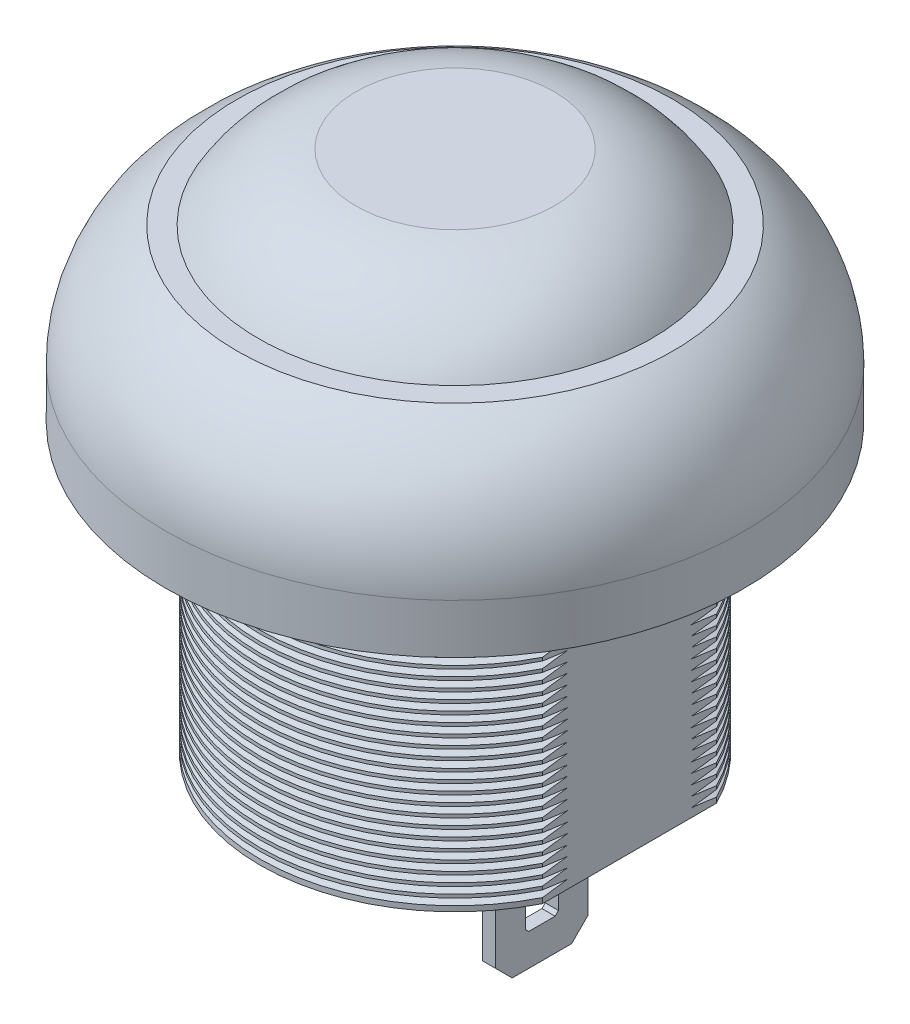
SolidWorks part; units mm, degrees
ref_plane "Front Plane" through (0, 0, 0) normal (0, 0, 1) x (1, 0, 0)
ref_plane "Top Plane" through (0, 0, 0) normal (0, 1, 0) x (1, 0, 0)
ref_plane "Right Plane" through (0, 0, 0) normal (1, 0, 0) x (0, 0, -1)
sketch "Sketch1" plane through (0, 0, 0) normal (0, 1, 0) x (1, 0, 0)
  circle A0 centre (0, 0) radius 8.75
  dimension "D1" = 17.5
extrude "Boss-Extrude1" add sketch "Sketch1" along normal blind 1.5
ref_plane "Plane1" through (0, 5.15, 0) normal (0, -1, 0) x (-1, 0, 0)
sketch "Sketch2" plane through (0, 5.15, 0) normal (0, -1, 0) x (-1, 0, 0)
  circle A0 centre (0, 0) radius 6.6
  dimension "D1" = 13.2
sketch "Sketch3" plane through (0, 0, 0) normal (0, 0, 1) x (1, 0, 0)
  line L0 (-6.6, 5.15) -> (6.6, 5.15) construction
  line L1 (-8.75, 1.5) -> (-8.75, 0) construction
  line L2 (-8.75, 0) -> (8.75, 0) construction
  line L3 (-8.75, 1.5) -> (0, 1.5)
  line L4 (8.75, 1.5) -> (-8.75, 1.5) construction
  line L5 (0, 1.5) -> (0, 5.15)
  line L6 (0, 5.15) -> (-6.6, 5.15)
  line L7 (0, 1.5) -> (0, 6.9701) construction
  arc A0 (-8.75, 1.5) -> (-6.6, 5.15) centre (-4.5767, 1.5) cw
revolve "Revolve1" add sketch "Sketch3" angle 360 about L7
ref_plane "Plane2" through (0, 7.15, 0) normal (0, 1, 0) x (1, 0, 0)
sketch "Sketch4" plane through (0, 7.15, 0) normal (0, 1, 0) x (1, 0, 0)
  circle A0 centre (0, 0) radius 3
  dimension "D1" = 6
sketch "Sketch5" plane through (0, 5.15, 0) normal (0, 1, 0) x (1, 0, 0)
  circle A0 centre (0, 0) radius 5.95
  dimension "D1" = 11.9
sketch "Sketch6" plane through (0, 0, 0) normal (0, 0, 1) x (1, 0, 0)
  line L0 (3, 7.15) -> (-3, 7.15) construction
  line L1 (5.95, 5.15) -> (-5.95, 5.15) construction
  line L2 (-3, 7.15) -> (0, 7.15)
  line L3 (0, 7.15) -> (0, 5.15)
  line L4 (0, 5.15) -> (-5.95, 5.15)
  line L5 (-5.95, 5.15) -> (-5.9731, 5.149)
  line L6 (0, 5.15) -> (0, 8.6522) construction
  arc A0 (-3, 7.15) -> (-5.95, 5.15) centre (-2.3574, 3.0265) ccw
  arc A1 (-6.6, 5.15) -> (-8.75, 1.5) centre (-4.5767, 1.5) ccw construction
revolve "Revolve2" add sketch "Sketch6" angle 360 about L6 region at (-2.5359, 6.0636, 0)
sketch "Sketch7" plane through (0, 0, 0) normal (0, -1, 0) x (1, 0, 0)
  circle A0 centre (0, 0) radius 6.61
  dimension "D1" = 13.22
extrude "Boss-Extrude2" add sketch "Sketch7" along normal blind 1.12
sketch "Sketch8" plane through (0, -1.12, 0) normal (0, -1, 0) x (1, 0, 0)
  circle A0 centre (0, 0) radius 5.9
  dimension "D1" = 11.8
extrude "Boss-Extrude3" add sketch "Sketch8" along normal blind 7.56
sketch "Sketch9" plane through (0, -8.68, 0) normal (0, -1, 0) x (1, 0, 0)
  circle A0 centre (0, 0) radius 4.34
  dimension "D1" = 8.68
extrude "Boss-Extrude4" add sketch "Sketch9" along normal blind 0.7
sketch "Sketch10" plane through (0, 0, 0) normal (0, 0, 1) x (1, 0, 0)
  line L0 (-4.34, -9.38) -> (4.34, -9.38) construction
  line L1 (-2.63, -9.38) -> (-2.23, -9.38)
  line L2 (-2.63, -9.38) -> (-2.63, -12.82)
  line L3 (-2.63, -12.82) -> (-2.23, -12.82)
  line L4 (-2.23, -9.38) -> (-2.23, -12.82)
  line L5 (-2.23, -9.38) -> (2.23, -9.38) construction
  line L6 (2.23, -9.38) -> (2.63, -9.38)
  line L7 (2.23, -9.38) -> (2.23, -12.82)
  line L8 (2.23, -12.82) -> (2.63, -12.82)
  line L9 (2.63, -9.38) -> (2.63, -12.82)
  line L10 (0, -9.38) -> (0, 0) construction
  dimension "D1" = 4.46
  dimension "D2" = 0.4
  dimension "D3" = 0.4
  dimension "D4" = 3.44
extrude "Boss-Extrude5" add sketch "Sketch10" along normal blind 1.4 and the other way blind 1.4
chamfer "Chamfer1" distance 0.5 distance2 0.5 4 edges at (-2.43, -12.82, -1.4) (-2.43, -12.82, 1.4) (2.43, -12.82, -1.4) (2.43, -12.82, 1.4)
sketch "Sketch11" plane through (2.63, 0, 0) normal (1, 0, 0) x (0, 0, -1)
  line L0 (0, -9.38) -> (0, -12.82) construction
  line L1 (1.4, -9.38) -> (-1.4, -9.38) construction
  line L2 (0.9, -12.82) -> (-0.9, -12.82) construction
  line L3 (0.5, -10.45) -> (0.4, -10.35)
  line L4 (-0.4, -11.85) -> (0.4, -11.85)
  line L5 (-0.5, -11.75) -> (-0.5, -10.45)
  line L6 (-0.4, -10.35) -> (0.4, -10.35)
  line L7 (0.5, -11.75) -> (0.5, -10.45)
  line L8 (-0.5, -11.85) -> (0.5, -10.35) construction
  line L9 (-0.5, -10.35) -> (0.5, -11.85) construction
  line L10 (-0.5, -10.45) -> (-0.4, -10.35)
  line L11 (-0.4, -11.85) -> (-0.5, -11.75)
  line L12 (0.4, -11.85) -> (0.5, -11.75)
  point P6 (0, -11.1)
  dimension "D1" = 1.5
  dimension "D2" = 1
extrude "Cut-Extrude1" cut sketch "Sketch11" against normal through all
sketch "Sketch12" plane through (0, -8.68, 0) normal (0, -1, 0) x (1, 0, 0)
  line L0 (5.28, 2.6328) -> (5.28, -2.6328)
  line L1 (-5.28, 2.6328) -> (-5.28, -2.6328)
  line L2 (-5.28, 0) -> (5.28, 0) construction
  arc A0 (5.28, -2.6328) -> (5.28, 2.6328) centre (0, 0) ccw
  circle A1 centre (0, 0) radius 5.9
  arc A2 (-5.28, 2.6328) -> (-5.28, -2.6328) centre (0, 0) ccw
  dimension "D2" = 10.56
  dimension "D1" = 0
extrude "Cut-Extrude2" cut sketch "Sketch12" against normal up to surface (7.56 mm away) up to face at (0, -1.12, -6.61)
sketch "Sketch13" plane through (0, -1.12, 0) normal (0, -1, 0) x (1, 0, 0)
  line L0 (-2.9803, 5.9) -> (2.9803, 5.9)
  arc A0 (5.28, 2.6328) -> (-5.28, 2.6328) centre (0, 0) ccw construction
  circle A1 centre (0, 0) radius 6.61
  arc A2 (2.9803, 5.9) -> (-2.9803, 5.9) centre (0, 0) ccw
  dimension "D1" = 0
extrude "Cut-Extrude3" cut sketch "Sketch13" against normal up to surface (1.12 mm away) up to face at (0, 0, 8.75)
sketch "Sketch14" plane through (0, 0, 0) normal (1, 0, 0) x (0, 0, -1)
  line L0 (-5.9, -1.12) -> (-5.6, -1.22)
  line L1 (-5.6, -1.22) -> (-5.9, -1.32)
  line L2 (-5.9, -1.12) -> (-5.9, -8.68) construction
  line L3 (-5.9, -1.32) -> (-5.9, -1.12)
  line L4 (-5.9, -1.22) -> (-5.6, -1.22) construction
  line L5 (-5.6, -1.52) -> (-5.9, -1.62)
  line L6 (-5.9, -1.42) -> (-5.6, -1.52)
  line L7 (-5.9, -1.62) -> (-5.9, -1.42)
  line L8 (-5.6, -1.82) -> (-5.9, -1.92)
  line L9 (-5.9, -1.72) -> (-5.6, -1.82)
  line L10 (-5.9, -1.92) -> (-5.9, -1.72)
  line L11 (-5.6, -2.12) -> (-5.9, -2.22)
  line L12 (-5.9, -2.02) -> (-5.6, -2.12)
  line L13 (-5.9, -2.22) -> (-5.9, -2.02)
  line L14 (-5.6, -2.42) -> (-5.9, -2.52)
  line L15 (-5.9, -2.32) -> (-5.6, -2.42)
  line L16 (-5.9, -2.52) -> (-5.9, -2.32)
  line L17 (-5.6, -2.72) -> (-5.9, -2.82)
  line L18 (-5.9, -2.62) -> (-5.6, -2.72)
  line L19 (-5.9, -2.82) -> (-5.9, -2.62)
  line L20 (-5.6, -3.02) -> (-5.9, -3.12)
  line L21 (-5.9, -2.92) -> (-5.6, -3.02)
  line L22 (-5.9, -3.12) -> (-5.9, -2.92)
  line L23 (-5.6, -3.32) -> (-5.9, -3.42)
  line L24 (-5.9, -3.22) -> (-5.6, -3.32)
  line L25 (-5.9, -3.42) -> (-5.9, -3.22)
  line L26 (-5.6, -3.62) -> (-5.9, -3.72)
  line L27 (-5.9, -3.52) -> (-5.6, -3.62)
  line L28 (-5.9, -3.72) -> (-5.9, -3.52)
  line L29 (-5.6, -3.92) -> (-5.9, -4.02)
  line L30 (-5.9, -3.82) -> (-5.6, -3.92)
  line L31 (-5.9, -4.02) -> (-5.9, -3.82)
  line L32 (-5.6, -4.22) -> (-5.9, -4.32)
  line L33 (-5.9, -4.12) -> (-5.6, -4.22)
  line L34 (-5.9, -4.32) -> (-5.9, -4.12)
  line L35 (-5.6, -4.52) -> (-5.9, -4.62)
  line L36 (-5.9, -4.42) -> (-5.6, -4.52)
  line L37 (-5.9, -4.62) -> (-5.9, -4.42)
  line L38 (-5.6, -4.82) -> (-5.9, -4.92)
  line L39 (-5.9, -4.72) -> (-5.6, -4.82)
  line L40 (-5.9, -4.92) -> (-5.9, -4.72)
  line L41 (-5.6, -5.12) -> (-5.9, -5.22)
  line L42 (-5.9, -5.02) -> (-5.6, -5.12)
  line L43 (-5.9, -5.22) -> (-5.9, -5.02)
  line L44 (-5.6, -5.42) -> (-5.9, -5.52)
  line L45 (-5.9, -5.32) -> (-5.6, -5.42)
  line L46 (-5.9, -5.52) -> (-5.9, -5.32)
  line L47 (-5.6, -5.72) -> (-5.9, -5.82)
  line L48 (-5.9, -5.62) -> (-5.6, -5.72)
  line L49 (-5.9, -5.82) -> (-5.9, -5.62)
  line L50 (-5.6, -6.02) -> (-5.9, -6.12)
  line L51 (-5.9, -5.92) -> (-5.6, -6.02)
  line L52 (-5.9, -6.12) -> (-5.9, -5.92)
  line L53 (-5.6, -6.32) -> (-5.9, -6.42)
  line L54 (-5.9, -6.22) -> (-5.6, -6.32)
  line L55 (-5.9, -6.42) -> (-5.9, -6.22)
  line L56 (-5.6, -6.62) -> (-5.9, -6.72)
  line L57 (-5.9, -6.52) -> (-5.6, -6.62)
  line L58 (-5.9, -6.72) -> (-5.9, -6.52)
  line L59 (-5.6, -6.92) -> (-5.9, -7.02)
  line L60 (-5.9, -6.82) -> (-5.6, -6.92)
  line L61 (-5.9, -7.02) -> (-5.9, -6.82)
  line L62 (-5.6, -7.22) -> (-5.9, -7.32)
  line L63 (-5.9, -7.12) -> (-5.6, -7.22)
  line L64 (-5.9, -7.32) -> (-5.9, -7.12)
  line L65 (-5.6, -7.52) -> (-5.9, -7.62)
  line L66 (-5.9, -7.42) -> (-5.6, -7.52)
  line L67 (-5.9, -7.62) -> (-5.9, -7.42)
  line L68 (-5.6, -7.82) -> (-5.9, -7.92)
  line L69 (-5.9, -7.72) -> (-5.6, -7.82)
  line L70 (-5.9, -7.92) -> (-5.9, -7.72)
  line L71 (-5.6, -8.12) -> (-5.9, -8.22)
  line L72 (-5.9, -8.02) -> (-5.6, -8.12)
  line L73 (-5.9, -8.22) -> (-5.9, -8.02)
  line L74 (-5.6, -8.42) -> (-5.9, -8.52)
  line L75 (-5.9, -8.32) -> (-5.6, -8.42)
  line L76 (-5.9, -8.52) -> (-5.9, -8.32)
  line L77 (0, 0) -> (0, -8.68) construction
  line L78 (-4.34, -8.68) -> (4.34, -8.68) construction
  dimension "D1" = 0.3
  dimension "D2" = 0.2
  dimension "D3" = 25
revolve "Cut-Revolve1" cut sketch "Sketch14" angle 360 about L77
